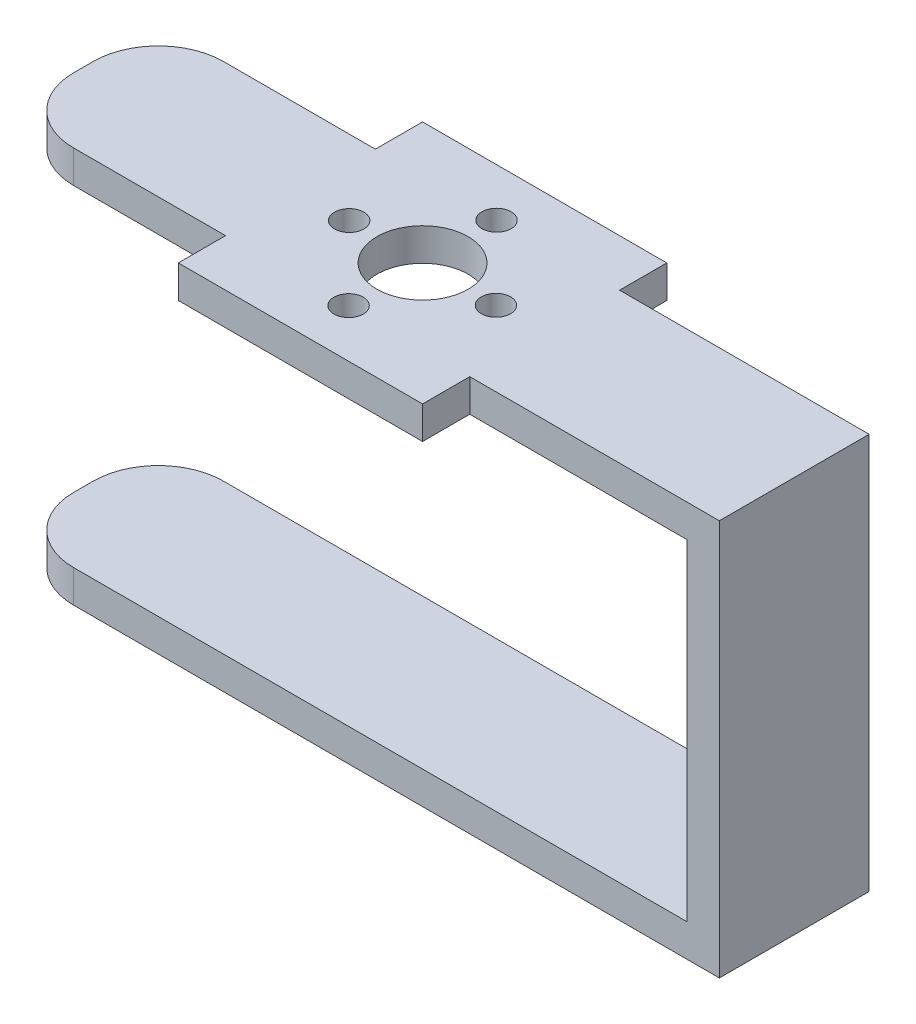
SolidWorks part; units mm, degrees
ref_plane "Front Plane" through (0, 0, 0) normal (0, 0, 1) x (1, 0, 0)
ref_plane "Top Plane" through (0, 0, 0) normal (0, 1, 0) x (1, 0, 0)
ref_plane "Right Plane" through (0, 0, 0) normal (1, 0, 0) x (0, 0, -1)
sketch "Sketch1" plane through (0, 0, 0) normal (0, 1, 0) x (1, 0, 0)
  line L0 (-71.3004, 0) -> (71.3004, 0) construction
  line L1 (18.75, 11.5) -> (57.07, 11.5)
  line L2 (18.75, 0) -> (57.07, 0)
  line L3 (18.75, 11.5) -> (18.75, -11.5)
  line L4 (18.75, -18.75) -> (-18.75, -18.75)
  line L5 (18.75, -18.75) -> (18.75, 18.75)
  line L6 (18.75, 18.75) -> (-18.75, 18.75)
  line L7 (-18.75, -18.75) -> (-18.75, 18.75)
  line L8 (18.75, -18.75) -> (-18.75, 18.75) construction
  line L9 (18.75, 18.75) -> (-18.75, -18.75) construction
  line L10 (18.75, -11.5) -> (57.07, -11.5)
  line L11 (57.07, 11.5) -> (57.07, -11.5)
  line L12 (0, 128.2858) -> (0, -128.2858) construction
  line L13 (-18.75, 11.5) -> (-18.75, -11.5)
  line L14 (-18.75, -11.5) -> (-57.07, -11.5)
  line L15 (-57.07, 11.5) -> (-57.07, -11.5)
  line L16 (-18.75, 11.5) -> (-57.07, 11.5)
  line L17 (-57.07, -11.5) -> (-52.07, -11.5)
  line L18 (57.07, 11.5) -> (52.07, 11.5)
  line L19 (57.07, 11.5) -> (57.07, -11.5)
  line L20 (57.07, -11.5) -> (52.07, -11.5)
  line L21 (52.07, 11.5) -> (52.07, -11.5)
  line L22 (-52.07, 11.5) -> (-52.07, -11.5)
  line L23 (-57.07, 11.5) -> (-52.07, 11.5)
  line L24 (-57.07, 11.5) -> (-57.07, -11.5)
  circle A0 centre (0, 0) radius 7
  circle A1 centre (0, 11.358) radius 2.25
  circle A2 centre (11.2692, 0) radius 2.25
  circle A3 centre (-11.2692, 0) radius 2.25
  circle A4 centre (0, -11.358) radius 2.25
  point P9 (0, 0)
  point P26 (0, 0)
  dimension "D1" = 14
  dimension "D2" = 4.5
  dimension "D5" = 4.5
  dimension "D3" = 11.358
  dimension "D4" = 16
  dimension "D6" = 16
  dimension "D7" = 16
  dimension "D8" = 37.5
  dimension "D9" = 37.5
  dimension "D10" = 11.5
  dimension "D11" = 38.32
  dimension "D12" = 5
extrude "Boss-Extrude2" add sketch "Sketch1" against normal blind 5 contours L16 L22 L14 L7 | L7 L4 L5 L3 L6 A4 A3 A2 A1 A0 | L21 L2 L3 L10 | L21 L1 L3 L2 region at (35.41, 0, -5.75) region at (18.2197, 0, -5.75) region at (35.41, 0, 5.75) region at (-35.41, 0, 0)
extrude "Boss-Extrude3" add sketch "Sketch1<3>" against normal blind 60.8 contours L2 L21 L10 L11 | L1 L21 L2 L11 region at (54.57, 0, -5.75) region at (54.57, 0, 5.75)
sketch "Sketch1<3>" plane through (0, 0, 0) normal (0, 1, 0) x (1, 0, 0) same geometry as "Sketch1"
sketch "Sketch2" plane through (-52.07, 0, 0) normal (-1, 0, 0) x (0, 0, 1)
  line L0 (11.5, 0) -> (11.5, -90.7316) construction
sketch "Sketch3" plane through (0, -60.8, 0) normal (0, -1, 0) x (1, 0, 0)
  line L1 (57.07, -11.5) -> (-52.07, -11.5)
  line L2 (57.07, -11.5) -> (57.07, 11.5)
  line L3 (57.07, 11.5) -> (-52.07, 11.5)
  line L4 (-52.07, -11.5) -> (-52.07, 11.5)
extrude "Boss-Extrude4" add sketch "Sketch3" against normal blind 5
sketch "Sketch4" plane through (0, -60.8, 0) normal (0, -1, 0) x (1, 0, 0)
  circle A0 centre (0, 0) radius 3
  dimension "D1" = 6
extrude "Boss-Extrude5" add sketch "Sketch4" along normal blind 5
fillet "Fillet3" radius 10 4 edges at (-52.07, -58.3, -11.5) (-52.07, -58.3, 11.5) (-52.07, -2.5, -11.5) (-52.07, -2.5, 11.5)
